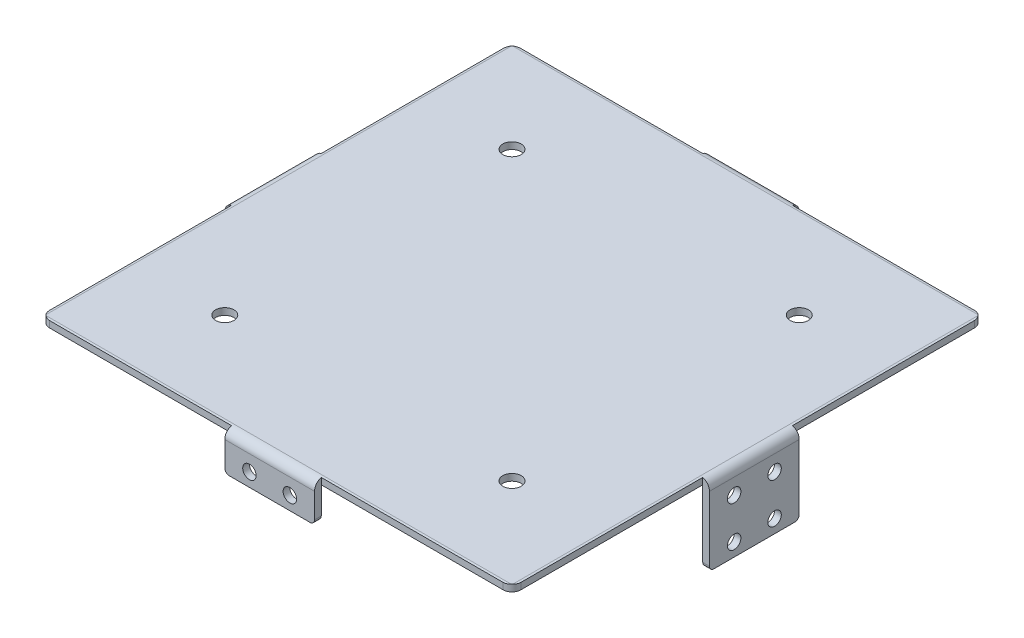
SolidWorks part; units mm, degrees
ref_plane "Front Plane" through (0, 0, 0) normal (0, 0, 1) x (1, 0, 0)
ref_plane "Top Plane" through (0, 0, 0) normal (0, 1, 0) x (1, 0, 0)
ref_plane "Right Plane" through (0, 0, 0) normal (1, 0, 0) x (0, 0, -1)
sketch "Sketch1" plane through (0, 0, 0) normal (0, 1, 0) x (1, 0, 0)
  line L1 (-52.5, -52.5) -> (52.5, -52.5)
  line L2 (-52.5, -52.5) -> (-52.5, 52.5)
  line L3 (-52.5, 52.5) -> (52.5, 52.5)
  line L4 (52.5, -52.5) -> (52.5, 52.5)
  line L5 (-52.5, -52.5) -> (52.5, 52.5) construction
  line L6 (-52.5, 52.5) -> (52.5, -52.5) construction
  point P0 (0, 0)
  dimension "D1" = 105
extrude "Boss-Extrude1" add sketch "Sketch1" along normal blind 1.5 contours L2 L1 L4 L3
sketch "Sketch2" plane through (0, 1.5, 0) normal (0, 1, 0) x (1, 0, 0)
  line L0 (-52.5, 52.5) -> (52.5, 52.5) construction
  line L1 (-10, 52.5) -> (10, 52.5)
  line L2 (-10, 52.5) -> (-10, 54)
  line L3 (-10, 54) -> (10, 54)
  line L4 (10, 52.5) -> (10, 54)
  line L5 (-52.5, -52.5) -> (-52.5, 52.5) construction
  line L6 (-52.5, 0) -> (52.5, 0) construction
  line L7 (52.5, -52.5) -> (52.5, 52.5) construction
  line L8 (-10, -54) -> (10, -54)
  line L9 (10, -52.5) -> (10, -54)
  line L10 (-10, -52.5) -> (10, -52.5)
  line L11 (-10, -52.5) -> (-10, -54)
  point P13 (0, 0)
  dimension "D1" = 20
  dimension "D2" = 42.5
  dimension "D3" = 1.5
sketch "Sketch3" plane through (0, 1.5, 0) normal (0, 1, 0) x (1, 0, 0)
  line L0 (0, 52.5) -> (0, -52.5) construction
  line L1 (-10, 52.5) -> (10, 52.5) construction
  line L2 (-10, -52.5) -> (10, -52.5) construction
  line L3 (52.5, -52.5) -> (52.5, 52.5) construction
  line L4 (52.5, -10) -> (54, -10)
  line L5 (52.5, -10) -> (52.5, 10)
  line L6 (52.5, 10) -> (54, 10)
  line L7 (54, -10) -> (54, 10)
  line L8 (-52.5, 52.5) -> (52.5, 52.5) construction
  line L9 (-52.5, 10) -> (-54, 10)
  line L10 (-54, -10) -> (-54, 10)
  line L11 (-52.5, -10) -> (-54, -10)
  line L12 (-52.5, -10) -> (-52.5, 10)
  dimension "D1" = 20
  dimension "D2" = 42.5
  dimension "D3" = 1.5
extrude "Boss-Extrude2" add sketch "Sketch2" against normal blind 8.5
extrude "Boss-Extrude3" add sketch "Sketch3" against normal blind 17.45
sketch "Sketch4" plane through (0, 0, 54) normal (0, 0, 1) x (1, 0, 0)
  line L0 (0, 1.5) -> (0, -7) construction
  line L1 (-10, 1.5) -> (10, 1.5) construction
  line L2 (-10, -7) -> (10, -7) construction
  line L3 (-52.5, 0) -> (-10, 0) construction
  circle A0 centre (-4.5, -4) radius 1.5
  circle A1 centre (4.5, -4) radius 1.5
  dimension "D1" = 3
  dimension "D2" = 4.5
  dimension "D3" = 4
extrude "Cut-Extrude1" cut sketch "Sketch4" against normal through all
sketch "Sketch5" plane through (54, 0, 0) normal (1, 0, 0) x (0, 0, -1)
  line L1 (-10, -15.95) -> (-10, 1.5) construction
  line L2 (0, 1.5) -> (0, -15.95) construction
  line L3 (-10, 1.5) -> (10, 1.5) construction
  line L4 (-10, -15.95) -> (10, -15.95) construction
  line L5 (10, -8.5) -> (-10, -8.5) construction
  line L6 (10, -15.95) -> (10, 1.5) construction
  circle A0 centre (-4.5, -4) radius 1.5
  circle A1 centre (4.5, -4) radius 1.5
  circle A2 centre (4.5, -13) radius 1.5
  circle A3 centre (-4.5, -13) radius 1.5
  dimension "D1" = 3
  dimension "D2" = 4.5
  dimension "D3" = 4.5
  dimension "D4" = 7.45
extrude "Cut-Extrude2" cut sketch "Sketch5" against normal through all
fillet "Fillet1" radius 1 8 edges at (-10, -7, -53.25) (10, -7, -53.25) (10, -7, 53.25) (-10, -7, 53.25) (53.25, -15.95, 10) (53.25, -15.95, -10) (-53.25, -15.95, -10) (-53.25, -15.95, 10)
fillet "Fillet2" radius 2 4 edges at (-54, 1.5, 0) (54, 1.5, 0) (0, 1.5, -54) (0, 1.5, 54)
fillet "Fillet3" radius 2 4 edges at (52.5, 0.7182, -52.5) (52.5, 0.7182, 52.5) (-52.5, 0.7182, 52.5) (-52.5, 0.7182, -52.5)
sketch "Sketch6" plane through (0, 1.5, 0) normal (0, 1, 0) x (1, 0, 0)
  line L4 (0, 0) -> (32, 0) construction
  line L5 (32, 0) -> (32, 32) construction
  line L6 (0, 0) -> (32, 32) construction
  circle A1 centre (-32, 32) radius 2.05
  circle A2 centre (32, 32) radius 2.05
  circle A3 centre (-32, -32) radius 2.05
  circle A4 centre (32, -32) radius 2.05
  dimension "D1" = 4.1
  dimension "D2" = 32
  dimension "D3" = 32
  dimension "D6" = 32
  dimension "D7" = 32
  dimension "D4" = 2
  dimension "D5" = 2
extrude "Holes for Bulkhead Rods" cut sketch "Sketch6" against normal blind 10
